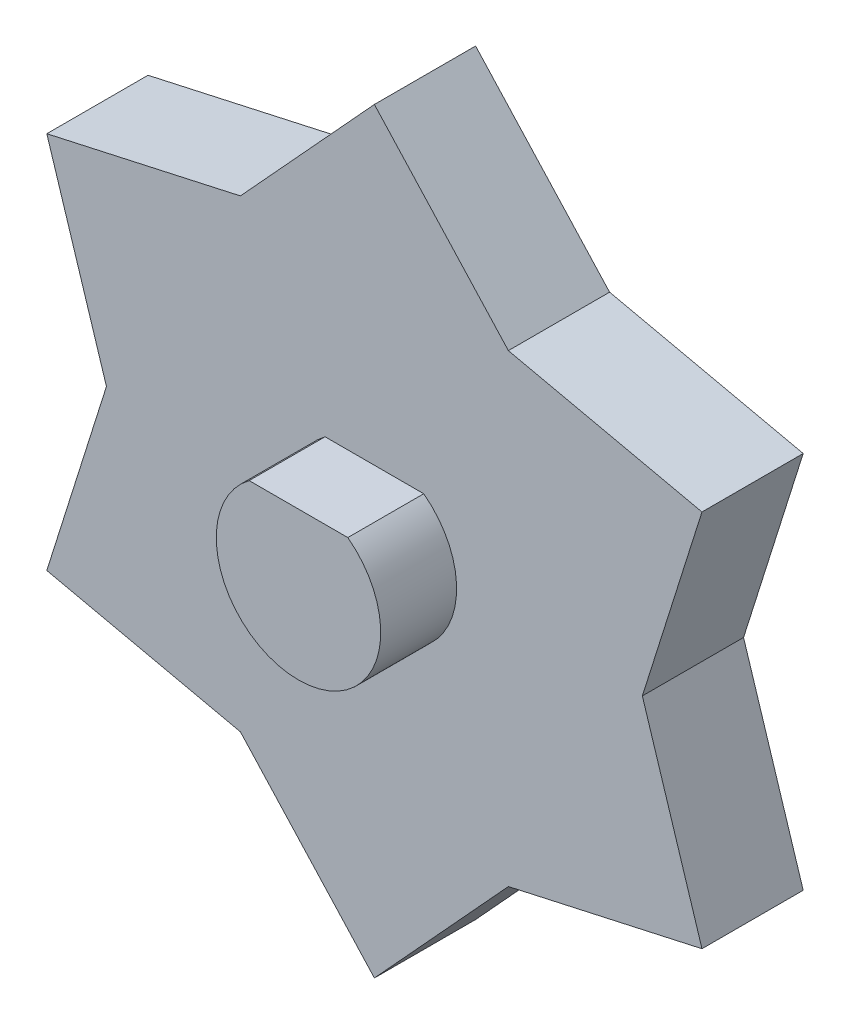
SolidWorks part; units mm, degrees
ref_plane "Front Plane" through (0, 0, 0) normal (0, 0, 1) x (1, 0, 0)
ref_plane "Top Plane" through (0, 0, 0) normal (0, 1, 0) x (1, 0, 0)
ref_plane "Right Plane" through (0, 0, 0) normal (1, 0, 0) x (0, 0, -1)
sketch "Sketch1" plane through (0, 0, 0) normal (0, 0, 1) x (1, 0, 0)
  line L0 (0, 7.4749) -> (0, -5.749) construction
  line L1 (-3.7233, 3.4117) -> (0, 7.4749)
  line L2 (0, 7.4749) -> (3.7233, 3.4117)
  line L3 (1.093, 4.9303) -> (6.4735, 3.7375)
  line L4 (6.4735, 3.7375) -> (4.8163, -1.5186)
  line L5 (4.8163, 1.5186) -> (6.4735, -3.7375)
  line L6 (6.4735, -3.7375) -> (1.093, -4.9303)
  line L7 (3.7233, -3.4117) -> (0, -7.4749)
  line L8 (0, -7.4749) -> (-3.7233, -3.4117)
  line L9 (-1.093, -4.9303) -> (-6.4735, -3.7375)
  line L10 (-6.4735, -3.7375) -> (-4.8163, 1.5186)
  line L11 (-4.8163, -1.5186) -> (-6.4735, 3.7375)
  line L12 (-6.4735, 3.7375) -> (-1.093, 4.9303)
  line L13 (0, 0) -> (1.65, 0) construction
  line L14 (-0.975, 1.3) -> (0.975, 1.3)
  circle A0 centre (0, 0) radius 1.05 construction
  circle A1 centre (0, 0) radius 5.05
  circle A2 centre (0, 0) radius 1.625
  point P26 (0, 0)
  dimension "D1" = 2.1
  dimension "D6" = 3.25
  dimension "D3" = 85
  dimension "D4" = 42.5
  dimension "D7" = 2.6
  dimension "D2" = 4
  dimension "D5" = 6
extrude "Boss-Extrude1" add sketch "Sketch1" against normal blind 2 contours A1 L1 L12 L11 L10 | L2 L0 A1 L3 | L0 L1 L12 A1 | A1 L12 L1 | A1 L2 L3 | A1 L5 L4 L3 L2 | L0 A1 A0 | A1 L11 L10 L9 L8 | A1 L10 L11 | A1 L8 L9 | A1 L9 L8 L7 L6 | A1 L6 L7 | A1 L7 L6 L5 L4 | A1 L4 L5 | A0 | A2 region at (-4.9664, 2.8673, 0) region at (-2.5502, 4.4171, 0) region at (-2.4536, 4.2497, 0) region at (0, 5.7347, 0) region at (-5.1004, 0, 0) region at (2.5502, 4.4171, 0) region at (-4.9664, -2.8673, 0) region at (4.9664, 2.8673, 0) region at (-2.5502, -4.4171, 0) region at (5.1004, 0, 0) region at (0, -5.7347, 0) region at (4.9664, -2.8673, 0) region at (2.5502, -4.4171, 0)
extrude "Boss-Extrude2" add sketch "Sketch1<4>" along normal blind 1.5 and the other way up to surface (2 mm away) contours A0 L0 | L0 A0 | L14 A2 region at (0, -0.0786, 0) other way up to face at (0, 0, -2)
sketch "Sketch1<4>" plane through (0, 0, 0) normal (0, 0, 1) x (1, 0, 0) same geometry as "Sketch1"
sketch "Sketch2" [suppressed] plane through (0, 0, 0) normal (0, 0, 1) x (1, 0, 0)
  line L0 (0, 0) -> (-9.2633, 0) construction
  line L1 (-0.5099, 1.25) -> (0.5099, 1.25)
  circle A0 centre (0, 0) radius 1.35
  dimension "D1" = 2.7
  dimension "D2" = 2.5
extrude "Cut-Extrude1" [suppressed] cut sketch "Sketch2" against normal through all contours A0 L0 | L0 A0 L1
